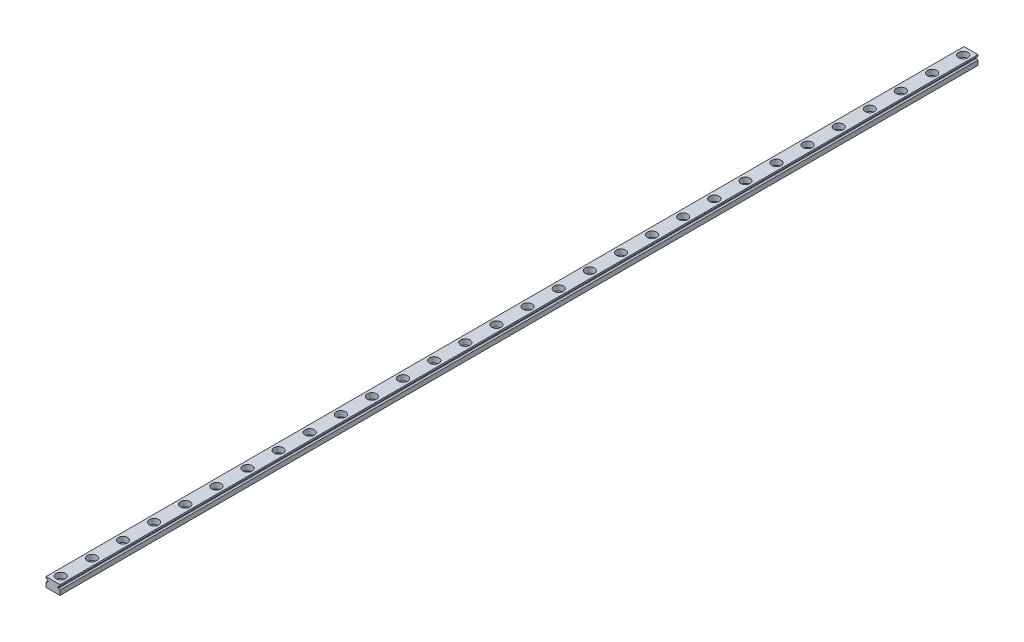
SolidWorks part; units mm, degrees
ref_plane "Front Plane" through (0, 0, 0) normal (0, 0, 1) x (1, 0, 0)
ref_plane "Top Plane" through (0, 0, 0) normal (0, 1, 0) x (1, 0, 0)
ref_plane "Right Plane" through (0, 0, 0) normal (1, 0, 0) x (0, 0, -1)
sketch "Sketch1" plane through (0, 0, 0) normal (0, 0, 1) x (1, 0, 0)
  line L0 (0, 0) -> (0, 5.7299) construction
  line L1 (-4.5, -3) -> (4.5, -3)
  line L2 (-4.5, -3) -> (-4.5, 0)
  line L3 (-4.5, 3) -> (4.5, 3)
  line L4 (4.5, -3) -> (4.5, 0)
  line L5 (-4.5, -3) -> (4.5, 3) construction
  line L6 (-4.5, 3) -> (4.5, -3) construction
  line L7 (-4.5, 2) -> (-4.5, 3)
  line L8 (-3.564, 0.648) -> (-3.2351, 0.648)
  line L9 (3.564, 0.648) -> (3.2351, 0.648)
  line L10 (-3.564, 1.352) -> (-3.2351, 1.352)
  line L11 (-3.2351, 0.648) -> (-3.2351, 1.352)
  line L12 (3.2351, 0.648) -> (3.2351, 1.352)
  line L13 (3.564, 1.352) -> (3.2351, 1.352)
  line L14 (4.5, 2) -> (4.5, 3)
  arc A0 (-3.564, 1.352) -> (-4.5, 2) centre (-4.5, 1) ccw
  arc A1 (-4.5, 0) -> (-3.564, 0.648) centre (-4.5, 1) ccw
  arc A2 (4.5, 0) -> (3.564, 0.648) centre (4.5, 1) cw
  arc A3 (3.564, 1.352) -> (4.5, 2) centre (4.5, 1) cw
  point P0 (0, 0)
  dimension "D3" = 1
  dimension "D1" = 9
  dimension "D2" = 6
  dimension "D4" = 2
extrude "Extrude1" add sketch "Sketch1" along normal blind 590
sketch "Sketch2" plane through (0, 3, 0) normal (0, 1, 0) x (1, 0, 0)
  line L0 (4.5, 0) -> (-4.5, 0) construction
  circle A0 centre (0, -5) radius 1.75
  circle A1 centre (0, -5) radius 3
  dimension "D1" = 3.5
  dimension "D2" = 6
  dimension "D3" = 5
extrude "Extrude2" cut sketch "Sketch2" against normal blind 3.5 contours A1
extrude "Extrude3" cut sketch "Sketch" against normal through all contours A0
sketch "Sketch" plane through (0, 3, 0) normal (0, 1, 0) x (1, 0, 0) same geometry as "Sketch2"
pattern_linear "LPattern1" count 30 spacing 20 along (0, 0, 1) of "Extrude2", "Extrude3"
